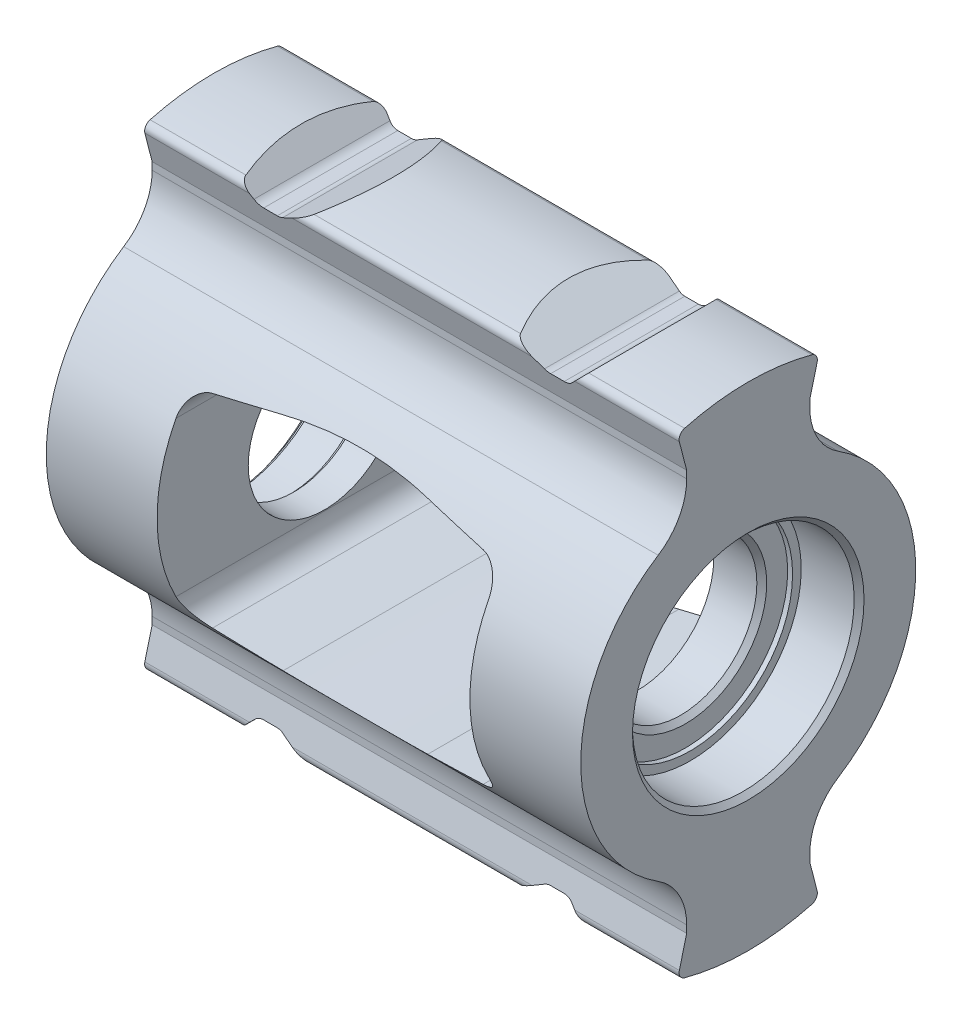
SolidWorks part; units mm, degrees
material "AISI 4340 Сталь, отожженная"
ref_plane "Спереди" through (0, 0, 0) normal (0, 0, 1) x (1, 0, 0)
ref_plane "Сверху" through (0, 0, 0) normal (0, 1, 0) x (1, 0, 0)
ref_plane "Справа" through (0, 0, 0) normal (1, 0, 0) x (0, 0, -1)
other "Центр тяжести"
sketch "Эскиз1" plane through (0, 0, 0) normal (1, 0, 0) x (0, 0, -1)
  line L0 (0, 0) -> (0, 100) construction
  line L1 (25, 0) -> (25, 18.3303)
  line L2 (-25, 0) -> (-25, 18.3303)
  line L3 (-25, 0) -> (-25, 100) construction
  line L4 (25, 0) -> (25, 100) construction
  line L5 (-25, 78.4156) -> (-25, 81.4156)
  line L6 (25, 78.4156) -> (25, 81.4156)
  line L7 (0, 0) -> (144.7557, 0) construction
  line L8 (-9.1971, 105.6542) -> (96.6389, 78.3275) construction
  line L9 (25, 81.4156) -> (28.7299, 95.8615)
  line L10 (-25, 81.4156) -> (-28.7299, 95.8615)
  line L11 (25, -81.4156) -> (28.7299, -95.8615)
  line L12 (25, -78.4156) -> (25, -81.4156)
  line L13 (-25, -81.4156) -> (-28.7299, -95.8615)
  line L14 (-25, -78.4156) -> (-25, -81.4156)
  circle A0 centre (0, 0) radius 31
  arc A1 (28.7114, 95.7896) -> (-28.7114, 95.7896) centre (0, 0) ccw
  arc A2 (-36.5591, 57.3361) -> (-36.5591, -57.3361) centre (0, 0) ccw
  arc A3 (36.5591, 57.3361) -> (25, 78.4156) centre (50, 78.4156) cw
  arc A4 (-36.5591, 57.3361) -> (-25, 78.4156) centre (-50, 78.4156) ccw
  arc A5 (36.5591, -57.3361) -> (25, -78.4156) centre (50, -78.4156) ccw
  arc A6 (-36.5591, -57.3361) -> (-25, -78.4156) centre (-50, -78.4156) cw
  arc A7 (36.5591, -57.3361) -> (36.5591, 57.3361) centre (0, 0) ccw
  arc A8 (-28.7114, -95.7896) -> (28.7114, -95.7896) centre (0, 0) ccw
  point P17 (25, 63.2376)
  point P20 (-25, 65.3835)
  point P36 (-25, -65.3835)
  dimension "D1" = 200
  dimension "D2" = 62
  dimension "D3" = 32
  dimension "D4" = 25
  dimension "D6" = 25
  dimension "D7" = 3
  dimension "D8" = 90
  dimension "D5" = 25
extrude "Бобышка-Вытянуть1" add sketch "Эскиз1" along normal blind 217 contours L13 A8 L11 L12 A5 A7 A3 L6 L9 A1 L10 L5 A4 A2 A6 L14 A0 region at (0, 79.9156, 22.5814)
sketch "Эскиз2" plane through (0, 0, 0) normal (0, 0, 1) x (1, 0, 0)
  line L0 (0, 0) -> (217, 0) construction
  line L1 (217, -57.3361) -> (217, 57.3361) construction
  line L2 (45, 40) -> (79.1441, 45)
  line L3 (172, -40) -> (45, -40) construction
  line L4 (172, -40) -> (172, 40)
  line L5 (172, 40) -> (45, 40) construction
  line L6 (45, -40) -> (45, 40)
  line L7 (172, -40) -> (45, 40) construction
  line L8 (172, 40) -> (45, -40) construction
  line L9 (79.1441, 45) -> (137.8559, 45) construction
  line L10 (137.8559, 45) -> (172, 40)
  line L11 (137.8559, -45) -> (172, -40)
  line L12 (45, -40) -> (79.1441, -45)
  line L13 (0, 81.4156) -> (108.5, 81.4156) construction
  line L14 (108.5, 81.4156) -> (108.5, 106.2417) construction
  line L15 (54.25, 81.4156) -> (54.25, 100) construction
  line L16 (217, 100) -> (0, 100) construction
  line L17 (35.55, 100) -> (72.95, 100)
  line L18 (54.25, 90) -> (45.4, 90)
  line L19 (45.4, 90) -> (35.55, 100)
  line L21 (54.25, 90) -> (72.95, 100)
  line L22 (162.75, 90) -> (171.6, 90)
  line L23 (171.6, 90) -> (181.45, 100)
  line L24 (181.45, 100) -> (144.05, 100)
  line L25 (162.75, 90) -> (144.05, 100)
  line L26 (54.25, -81.4156) -> (54.25, -100) construction
  line L27 (108.5, -81.4156) -> (108.5, -106.2417) construction
  line L28 (0, -81.4156) -> (108.5, -81.4156) construction
  line L29 (162.75, -90) -> (144.05, -100)
  line L30 (181.45, -100) -> (144.05, -100)
  line L31 (171.6, -90) -> (181.45, -100)
  line L32 (162.75, -90) -> (171.6, -90)
  line L33 (54.25, -90) -> (72.95, -100)
  line L34 (45.4, -90) -> (35.55, -100)
  line L35 (54.25, -90) -> (45.4, -90)
  line L36 (35.55, -100) -> (72.95, -100)
  line L37 (0, 57.3361) -> (0, -57.3361) construction
  arc A0 (79.1441, 45) -> (137.8559, 45) centre (108.5, -152.8338) cw
  arc A1 (79.1441, -45) -> (137.8559, -45) centre (108.5, 152.8338) ccw
  point P5 (108.5, 0)
  point P28 (54.25, 100)
  point P31 (54.25, 90)
  point P48 (54.25, -90)
  point P49 (54.25, -100)
  dimension "D4" = 200
  dimension "D1" = 80
  dimension "D2" = 45
  dimension "D3" = 5
  dimension "D5" = 37.4
  dimension "D6" = 10
extrude "Вырез-Вытянуть1" cut sketch "Эскиз2" against normal through all both and the other way through all
sketch "Эскиз4" plane through (0, 0, 0) normal (-1, 0, 0) x (0, 0, 1)
  circle A0 centre (0, 0) radius 45
  dimension "D1" = 90
extrude "Вырез-Вытянуть2" cut sketch "Эскиз4" against normal blind 28.5 and the other way through all
sketch "Эскиз6" plane through (217, 0, 0) normal (1, 0, 0) x (0, 0, -1)
  circle A0 centre (0, 0) radius 45
  dimension "D1" = 90
extrude "Вырез-Вытянуть3" cut sketch "Эскиз6" against normal blind 23.5
sketch "Эскиз9" plane through (0, 0, 0) normal (-1, 0, 0) x (0, 0, 1)
  circle A0 centre (0, 0) radius 57.5
  point P0 (0, 57.5)
  dimension "D1" = 115
hole_wizard "Отверстие обработанное метчиком M81" positions "Эскиз9" profile "Эскиз8" tap size "M8" standard "IS"
sketch "Эскиз8" plane through (0, 57.5, 0) normal (0, 1, 0) x (0, 0, 1)
  line L0 (0, 0) -> (0, 34.0429)
  line L1 (0, 34.0429) -> (3.4, 32)
  line L2 (3.4, 32) -> (3.4, 0.625)
  line L3 (3.4, 0.625) -> (4.025, 0)
  line L5 (4.025, 0) -> (0, 0)
  line L6 (-3.4, 0.625) -> (-4.025, 0) construction
  line L10 (0, 34.0429) -> (-3.4, 32) construction
  line L11 (0, -6.35) -> (0, 107.95) construction
  dimension "Диаметр сверла" = 6.8
  dimension "Глубина сверла" = 32
  dimension "Диаметр передней зенковки" = 8.05
  dimension "Угол передней зенковки" = 90
  dimension "Угол заточки сверла" = 118
cosmetic thread "Отверстие резьбы1" parameters "D1"=27, "D2"=8
pattern_circular "Круговой массив1" count 6 over 360 about axis through (217, 0, 0) along (-1, 0, 0) of "Отверстие обработанное метчиком M81"
sketch "Эскиз11" plane through (28.5, 0, 0) normal (-1, 0, 0) x (0, 0, 1)
  circle A0 centre (0, 0) radius 41.5
  dimension "D1" = 83
extrude "Вырез-Вытянуть4" cut sketch "Эскиз11" against normal blind 2
sketch "Эскиз12" plane through (193.5, 0, 0) normal (1, 0, 0) x (0, 0, -1)
  circle A0 centre (0, 0) radius 41.5
  dimension "D1" = 83
extrude "Вырез-Вытянуть5" cut sketch "Эскиз12" against normal blind 2
fillet "Скругление1" radius 5 8 edges at (171.6, 90, 0) (162.75, 90, 0) (54.25, 90, 0) (45.4, 90, 0) (54.25, -90, 0) (45.4, -90, 0) (162.75, -90, 0) (171.6, -90, 0)
fillet "Скругление3" radius 10 4 edges at (45, 40, 0) (172, 40, 0) (45, -40, 0) (172, -40, 0)
sketch "Эскиз13" plane through (0, 0, 0) normal (-1, 0, 0) x (0, 0, 1)
  circle A0 centre (0, 0) radius 45
  circle A1 centre (0, 0) radius 51.5
  circle A2 centre (0, 0) radius 45 construction
  dimension "D1" = 103
extrude "Вырез-Вытянуть6" cut sketch "Эскиз13" against normal blind 5
chamfer "Фаска1" distance 2 angle 45 5 edges at (191.5, 0, -31) (217, 0, -45) (30.5, 0, 31) (5, 0, 45) (0, 0, 51.5)
fillet "Скругление5" radius 3 12 edges at (19.8486, -95.7896, 28.7114) (108.5, -95.7896, 28.7114) (197.1514, -95.7896, 28.7114) (19.8486, -95.7896, -28.7114) (108.5, -95.7896, -28.7114) (197.1514, -95.7896, -28.7114) (19.8486, 95.7896, 28.7114) (108.5, 95.7896, 28.7114) (197.1514, 95.7896, 28.7114) (19.8486, 95.7896, -28.7114) (108.5, 95.7896, -28.7114) (197.1514, 95.7896, -28.7114)
